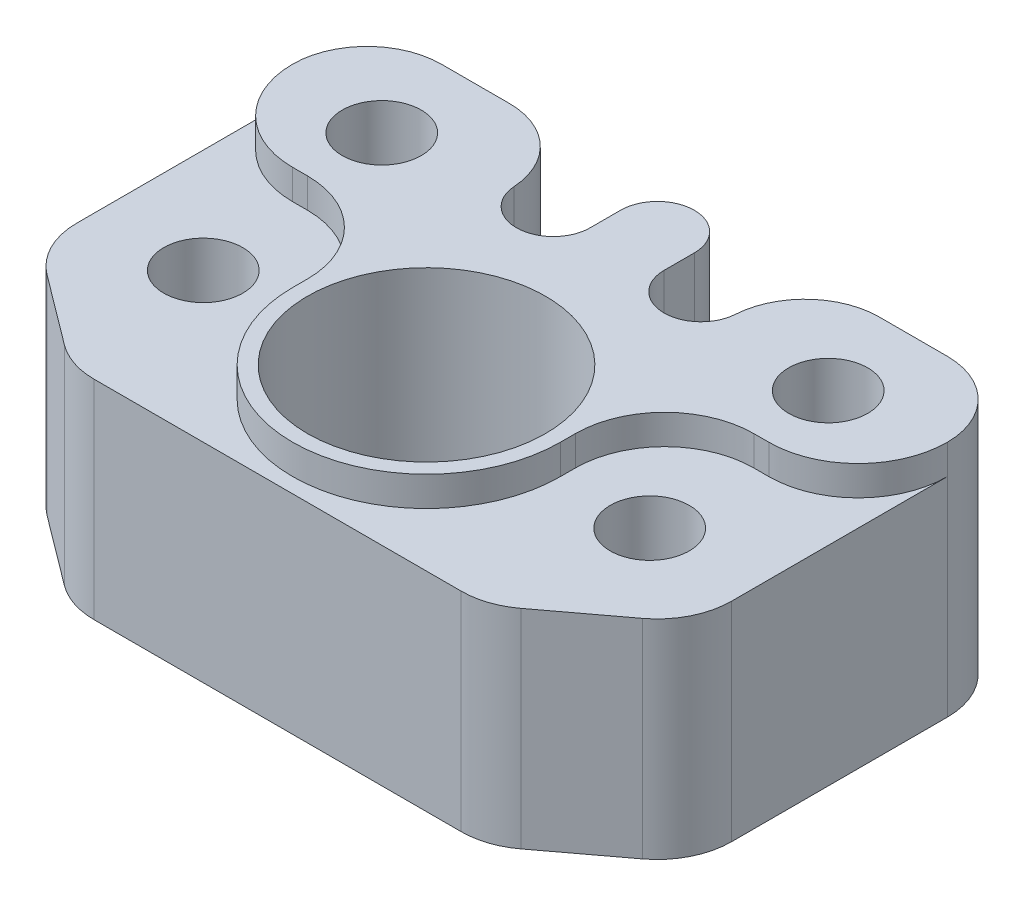
SolidWorks part; units mm, degrees
material "1060 Alloy"
ref_plane "Front Plane" through (0, 0, 0) normal (0, 0, 1) x (1, 0, 0)
ref_plane "Top Plane" through (0, 0, 0) normal (0, 1, 0) x (1, 0, 0)
ref_plane "Right Plane" through (0, 0, 0) normal (1, 0, 0) x (0, 0, -1)
sketch "Sketch1" plane through (0, 0, 0) normal (0, 1, 0) x (1, 0, 0)
  line L0 (0, 0) -> (-23.8125, 0) construction
  line L1 (0, 0) -> (23.8125, 0) construction
  line L2 (-34.925, -15.875) -> (-34.925, 28.575)
  line L3 (-34.925, -15.875) -> (34.925, -15.875)
  line L4 (-34.925, 28.575) -> (34.925, 28.575)
  line L5 (34.925, 28.575) -> (34.925, -15.875)
  line L6 (-7.9375, 7.9248) -> (-34.925, 7.9248) construction
  line L7 (7.9375, 7.9248) -> (34.925, 7.9248) construction
  line L8 (-11.811, 28.575) -> (-11.811, 17.4625)
  line L9 (-11.811, 17.4625) -> (-3.937, 17.4625)
  line L10 (-3.937, 17.4625) -> (-3.937, 28.575)
  line L11 (3.937, 28.575) -> (3.937, 17.4625)
  line L12 (3.937, 17.4625) -> (11.811, 17.4625)
  line L13 (11.811, 17.4625) -> (11.811, 28.575)
  line L14 (-34.925, -6.35) -> (-22.225, -15.875)
  line L15 (34.925, -6.35) -> (22.225, -15.875)
  line L16 (11.811, 17.4625) -> (34.925, 17.4625) construction
  line L17 (-11.811, 17.4625) -> (-34.925, 17.4625) construction
  circle A0 centre (0, 0) radius 14.2875
  circle A1 centre (-23.8125, 0) radius 5.2754
  circle A2 centre (23.8125, 0) radius 5.2754
  circle A3 centre (-23.8252, 19.05) radius 4.1672
  circle A4 centre (23.7998, 19.05) radius 4.1672
  circle A6 centre (-7.9375, 7.9248) radius 3.3655
  circle A7 centre (7.9375, 7.9248) radius 3.3655
  circle A8 centre (0, 0) radius 12.7
  dimension "D1" = 28.575
  dimension "D2" = 10.5508
  dimension "D4" = 34.925
  dimension "D7" = 11.0998
  dimension "D9" = 8.3344
  dimension "D10" = 8.3344
  dimension "D12" = 25.4
  dimension "D14" = 15.875
  dimension "D15" = 6.731
  dimension "D3" = 47.625
  dimension "D5" = 44.45
  dimension "D6" = 15.875
  dimension "D8" = 19.05
  dimension "D11" = 47.625
  dimension "D13" = 34.925
  dimension "D16" = 23.7998
  dimension "D17" = 7.874
  dimension "D18" = 7.874
  dimension "D19" = 44.45
  dimension "D20" = 9.525
  dimension "D21" = 11.1125
  dimension "D22" = 7.874
sketch "Sketch2" plane through (0, 0, 0) normal (0, 1, 0) x (1, 0, 0)
  line L0 (-34.925, 28.575) -> (34.925, 28.575) construction
  line L1 (34.925, 28.575) -> (34.925, -15.875) construction
  line L2 (-34.925, -15.875) -> (34.925, -15.875) construction
  line L3 (34.925, -6.35) -> (22.225, -15.875) construction
  line L4 (-34.925, -6.35) -> (-22.225, -15.875) construction
  line L5 (-34.925, -15.875) -> (-34.925, 28.575) construction
  line L6 (-34.925, 28.575) -> (-11.811, 28.575)
  line L7 (34.925, 28.575) -> (34.925, -6.35)
  line L8 (-22.225, -15.875) -> (22.225, -15.875)
  line L9 (34.925, -6.35) -> (22.225, -15.875)
  line L10 (-34.925, -6.35) -> (-22.225, -15.875)
  line L11 (-34.925, -6.35) -> (-34.925, 28.575)
  line L12 (11.811, 17.4625) -> (11.811, 28.575) construction
  line L13 (3.937, 17.4625) -> (11.811, 17.4625) construction
  line L14 (3.937, 28.575) -> (3.937, 17.4625) construction
  line L15 (-3.937, 17.4625) -> (-3.937, 28.575) construction
  line L16 (-11.811, 17.4625) -> (-3.937, 17.4625) construction
  line L17 (-11.811, 28.575) -> (-11.811, 17.4625) construction
  line L18 (11.811, 17.4625) -> (11.811, 28.575)
  line L19 (3.937, 17.4625) -> (11.811, 17.4625)
  line L20 (3.937, 28.575) -> (3.937, 17.4625)
  line L21 (-3.937, 17.4625) -> (-3.937, 28.575)
  line L22 (-11.811, 17.4625) -> (-3.937, 17.4625)
  line L23 (-11.811, 28.575) -> (-11.811, 17.4625)
  line L24 (-3.937, 28.575) -> (3.937, 28.575)
  line L25 (11.811, 28.575) -> (34.925, 28.575)
extrude "Boss-Extrude1" add sketch "Sketch2" against normal blind 22.225
fillet "Fillet1" radius 3.937 6 edges at (3.937, -11.1125, -28.575) (-3.937, -11.1125, -28.575) (11.811, -11.1125, -17.4625) (3.937, -11.1125, -17.4625) (-3.937, -11.1125, -17.4625) (-11.811, -11.1125, -17.4625)
fillet "Fillet3" radius 7.9375 8 edges at (22.225, -11.1125, 15.875) (-22.225, -11.1125, 15.875) (-34.925, -11.1125, 6.35) (34.925, -11.1125, 6.35) (34.925, -11.1125, -28.575) (-34.925, -11.1125, -28.575) (-11.811, -11.1125, -28.575) (11.811, -11.1125, -28.575)
hole_wizard "5/16 Clearance Hole1" positions "Sketch6" profile "Sketch7" hole size "5/16" standard "ANSI Inch" end condition through all
sketch "Sketch6" plane through (0, 0, 0) normal (0, 1, 0) x (1, 0, 0)
  point P0 (-23.8252, 19.05)
  point P3 (23.7998, 19.05)
sketch "Sketch7" plane through (-23.8252, 0, -19.05) normal (1, 0, 0) x (0, 0, 1)
  line L0 (0, 0) -> (0, 22.225)
  line L1 (0, 22.225) -> (4.2164, 22.225)
  line L2 (4.2164, 22.225) -> (4.2164, 0)
  line L5 (4.2164, 0) -> (0, 0)
  line L11 (0, -6.35) -> (0, 107.95) construction
  dimension "Thru Hole Dia." = 8.4328
  dimension "Thru Hole Depth" = 22.225
sketch "Sketch8" plane through (0, 0, 0) normal (0, 1, 0) x (1, 0, 0)
  line L0 (-26.9875, 20.6375) -> (-34.925, 20.6375) construction
  line L1 (-14.2875, 0) -> (14.2875, 0) construction
  line L2 (-25.4, 20.6375) -> (-34.925, 20.6375) construction
  line L3 (-25.4, 20.6375) -> (-25.4, 11.1125) construction
  line L4 (-25.4, 11.1125) -> (-14.2875, 11.1125)
  line L5 (-14.2875, 11.1125) -> (-14.2875, 0)
  line L6 (14.2875, 0) -> (14.2875, 11.1125)
  line L7 (0, -15.875) -> (0, 28.575) construction
  line L8 (-34.925, -15.875) -> (34.925, -15.875) construction
  line L9 (26.9875, 28.575) -> (19.724, 28.575) construction
  line L10 (3.937, 21.3995) -> (3.937, 24.638) construction
  line L11 (-3.937, 24.638) -> (-3.937, 21.3995) construction
  line L12 (-19.724, 28.575) -> (-26.9875, 28.575) construction
  line L13 (26.9875, 28.575) -> (19.724, 28.575)
  line L14 (3.937, 21.3995) -> (3.937, 24.638)
  line L15 (-3.937, 24.638) -> (-3.937, 21.3995)
  line L16 (-19.724, 28.575) -> (-26.9875, 28.575)
  line L17 (14.2875, 11.1125) -> (25.4, 11.1125)
  circle A2 centre (-26.9875, 20.6375) radius 7.9375 construction
  arc A3 (-26.9875, 28.575) -> (-34.925, 20.6375) centre (-26.9875, 20.6375) ccw construction
  circle A6 centre (0, 0) radius 14.2875 construction
  circle A7 centre (0, 0) radius 14.2875
  arc A8 (-34.925, 20.6375) -> (-26.9875, 28.575) centre (-26.9875, 20.6375) cw
  circle A9 centre (-25.4, 20.6375) radius 9.525 construction
  arc A10 (-34.925, 20.6375) -> (-25.4, 11.1125) centre (-25.4, 20.6375) ccw
  arc A13 (3.937, 24.638) -> (0, 28.575) centre (0, 24.638) ccw construction
  arc A14 (0, 28.575) -> (-3.937, 24.638) centre (0, 24.638) ccw construction
  arc A15 (3.937, 24.638) -> (0, 28.575) centre (0, 24.638) ccw
  arc A16 (0, 28.575) -> (-3.937, 24.638) centre (0, 24.638) ccw
  arc A17 (34.925, 20.6375) -> (25.4, 11.1125) centre (25.4, 20.6375) cw
  arc A18 (34.925, 20.6375) -> (26.9875, 28.575) centre (26.9875, 20.6375) ccw
  arc A19 (19.724, 28.575) -> (11.8029, 21.1469) centre (19.724, 20.6375) ccw construction
  arc A20 (7.874, 17.4625) -> (11.8029, 21.1469) centre (7.874, 21.3995) ccw construction
  arc A21 (3.937, 21.3995) -> (7.874, 17.4625) centre (7.874, 21.3995) ccw construction
  arc A24 (-7.874, 17.4625) -> (-3.937, 21.3995) centre (-7.874, 21.3995) ccw construction
  arc A25 (-11.8029, 21.1469) -> (-7.874, 17.4625) centre (-7.874, 21.3995) ccw construction
  arc A26 (-11.8029, 21.1469) -> (-19.724, 28.575) centre (-19.724, 20.6375) ccw construction
  arc A27 (19.724, 28.575) -> (11.8029, 21.1469) centre (19.724, 20.6375) ccw
  arc A28 (7.874, 17.4625) -> (11.8029, 21.1469) centre (7.874, 21.3995) ccw
  arc A29 (3.937, 21.3995) -> (7.874, 17.4625) centre (7.874, 21.3995) ccw
  arc A32 (-7.874, 17.4625) -> (-3.937, 21.3995) centre (-7.874, 21.3995) ccw
  arc A33 (-11.8029, 21.1469) -> (-7.874, 17.4625) centre (-7.874, 21.3995) ccw
  arc A34 (-11.8029, 21.1469) -> (-19.724, 28.575) centre (-19.724, 20.6375) ccw
  circle M1 centre (-23.8252, 19.05) radius 4.2164
  line M3 (26.9875, 28.575) -> (19.724, 28.575)
  arc M4 (19.724, 28.575) -> (11.8029, 21.1469) centre (19.724, 20.6375) ccw
  arc M5 (11.8029, 21.1469) -> (7.874, 17.4625) centre (7.874, 21.3995) cw
  arc M6 (7.874, 17.4625) -> (3.937, 21.3995) centre (7.874, 21.3995) cw
  line M7 (3.937, 21.3995) -> (3.937, 24.638)
  line M10 (-3.937, 24.638) -> (-3.937, 21.3995)
  arc M11 (-3.937, 21.3995) -> (-7.874, 17.4625) centre (-7.874, 21.3995) cw
  arc M12 (-7.874, 17.4625) -> (-11.8029, 21.1469) centre (-7.874, 21.3995) cw
  arc M13 (-11.8029, 21.1469) -> (-19.724, 28.575) centre (-19.724, 20.6375) ccw
  line M14 (-19.724, 28.575) -> (-26.9875, 28.575)
  arc M15 (-26.9875, 28.575) -> (-34.925, 20.6375) centre (-26.9875, 20.6375) ccw
  arc M25 (34.925, 20.6375) -> (26.9875, 28.575) centre (26.9875, 20.6375) ccw
  circle M27 centre (23.7998, 19.05) radius 4.2164
  dimension "D1" = 19.05
extrude "Boss-Extrude2" add sketch "Sketch8" along normal blind 3.175 contours A17 A10 A7 M25 M3 M4 M5 M6 M7 M10 M11 M12 M13 M14 M15 M27 M1 | A7 region at (0.0017, 0, -18.9256) region at (0, 0, 0)
fillet "Fillet4" radius 9.525 1 edges at (-14.2875, 1.5875, -11.1125) type face fillet first side face at (-19.8438, 1.5875, -11.1125) second side face at (-14.2875, 1.5875, -5.5562)
fillet "Fillet5" radius 9.525 1 edges at (14.2875, 1.5875, -11.1125) type face fillet first side face at (19.8438, 1.5875, -11.1125) second side face at (14.2875, 1.5875, -5.5562)
sketch "Sketch9" plane through (0, 3.175, 0) normal (0, 1, 0) x (1, 0, 0)
  circle A0 centre (0, 0) radius 12.7 construction
  circle A1 centre (0, 0) radius 12.7
extrude "Cut-Extrude1" cut sketch "Sketch9" against normal blind 19.177
hole_wizard "CSK for 5/16 Flat Head Machine Screw (100)2" positions "Sketch10" profile "Sketch11" countersink size "5/16" standard "ANSI Inch" end condition through all
sketch "Sketch10" plane through (0, -22.225, 0) normal (0, -1, 0) x (-1, 0, 0)
  point P0 (-23.8125, 0)
  point P3 (23.8125, 0)
sketch "Sketch11" plane through (23.8125, -22.225, 0) normal (1, 0, 0) x (0, 0, -1)
  line L0 (0, 0) -> (0, 25.4)
  line L1 (0, 25.4) -> (4.2164, 25.4)
  line L2 (4.2164, 25.4) -> (4.2164, 3.2289)
  line L3 (4.2164, 3.2289) -> (8.0645, 0)
  line L5 (8.0645, 0) -> (0, 0)
  line L6 (-4.2164, 3.2289) -> (-8.0645, 0) construction
  line L11 (0, -6.35) -> (0, 107.95) construction
  dimension "Thru Hole Dia." = 8.4328
  dimension "Thru Hole Depth" = 25.4
  dimension "Near C'Sink Dia." = 16.129
  dimension "Near C'Sink Angle" = 100
